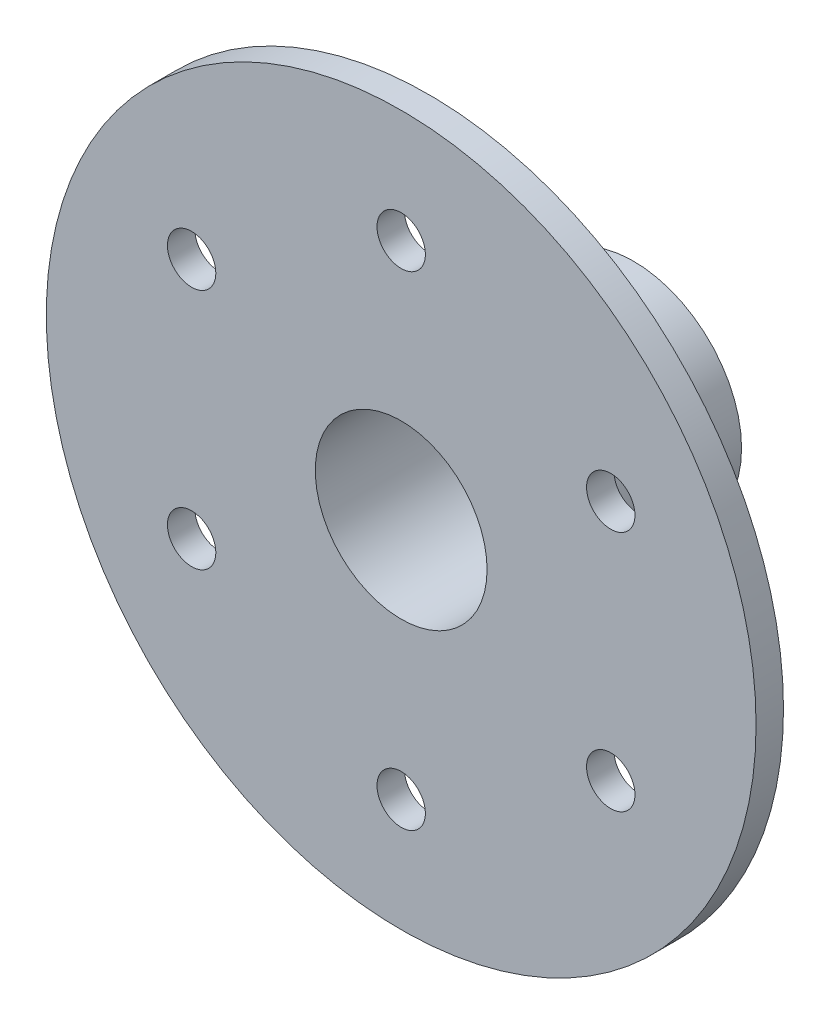
SolidWorks part; units mm, degrees
material "PVC Rígido"
ref_plane "Alzado" through (0, 0, 0) normal (0, 0, 1) x (1, 0, 0)
ref_plane "Planta" through (0, 0, 0) normal (0, 1, 0) x (1, 0, 0)
ref_plane "Vista lateral" through (0, 0, 0) normal (1, 0, 0) x (0, 0, -1)
sketch "Croquis1" plane through (0, 0, 0) normal (0, 0, 1) x (1, 0, 0)
  circle A0 centre (0, 0) radius 10.65
  circle A1 centre (0, 0) radius 13.4
  dimension "D1" = 21.3
  dimension "D2" = 26.8
extrude "Saliente-Extruir1" add sketch "Croquis1" along normal blind 25.4
sketch "Croquis2" plane through (0, 0, 25.4) normal (0, 0, 1) x (1, 0, 0)
  line L0 (0, 0) -> (0, 30) construction
  circle A0 centre (0, 0) radius 10.65
  circle A1 centre (0, 0) radius 44
  circle A3 centre (0, 30) radius 3
  circle A9 centre (25.9808, 15) radius 3
  circle A10 centre (25.9808, -15) radius 3
  circle A11 centre (0, -30) radius 3
  circle A12 centre (-25.9808, -15) radius 3
  circle A13 centre (-25.9808, 15) radius 3
  point P18 (0, 0)
  dimension "D1" = 21.3
  dimension "D2" = 88
  dimension "D3" = 30
  dimension "D4" = 6
  dimension "D5" = 6
extrude "Saliente-Extruir2" add sketch "Croquis2" along normal blind 3.4
